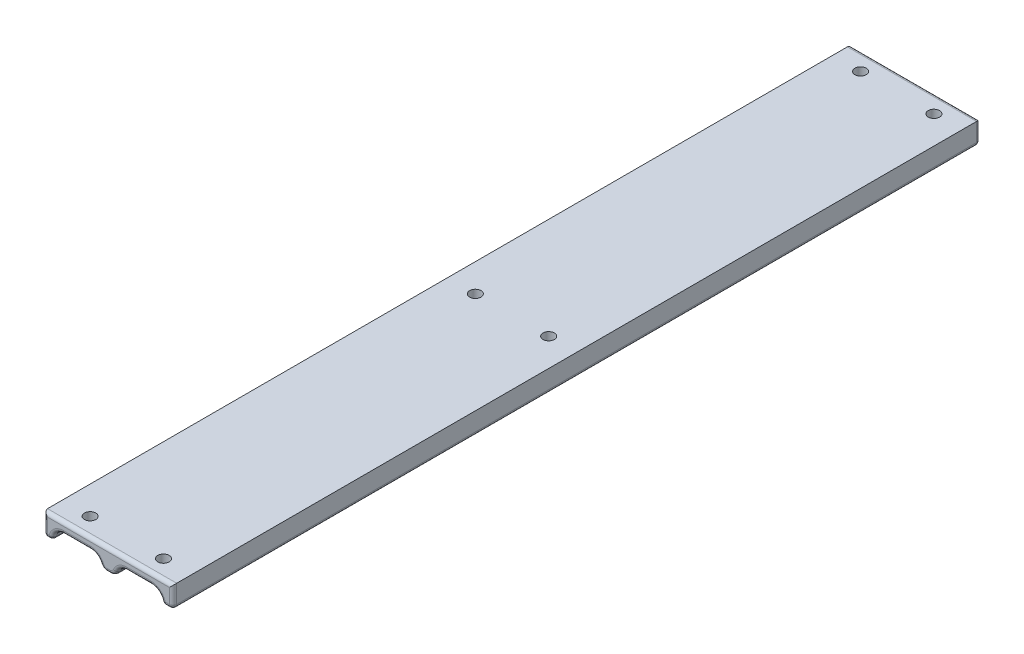
SolidWorks part; units mm, degrees
ref_plane "前视基准面" through (0, 0, 0) normal (0, 0, 1) x (1, 0, 0)
ref_plane "上视基准面" through (0, 0, 0) normal (0, 1, 0) x (1, 0, 0)
ref_plane "右视基准面" through (0, 0, 0) normal (1, 0, 0) x (0, 0, -1)
sketch "草图1" plane through (0, 0, 0) normal (0, 1, 0) x (1, 0, 0)
  line L0 (-17.6041, -110) -> (17.6041, -110)
  line L1 (17.6041, -110) -> (17.6041, 110)
  line L2 (17.6041, 110) -> (-17.6041, 110)
  line L3 (-17.6041, 110) -> (-17.6041, -110)
  circle A0 centre (10, -105) radius 1.55
  circle A1 centre (-10, -105) radius 1.55
  circle A2 centre (10, 0) radius 1.55
  circle A3 centre (-10, 0) radius 1.55
  circle A4 centre (10, 105) radius 1.55
  circle A5 centre (-10, 105) radius 1.55
extrude "凸台-拉伸1" add sketch "草图1" along normal blind 3
sketch "草图2" plane through (0, 0, 0) normal (0, -1, 0) x (1, 0, 0)
  line L1 (-17.6041, 110) -> (-15.2584, 110)
  line L2 (-17.6041, 110) -> (-17.6041, -110)
  line L3 (-17.6041, -110) -> (-15.2584, -110)
  line L4 (-17.6041, 110) -> (-17.6041, -110)
  line L5 (-17.6041, -110) -> (17.6041, -110)
  line L6 (17.6041, -110) -> (17.6041, 110)
  line L7 (17.6041, 110) -> (-17.6041, 110)
  line L8 (-17.6041, 110) -> (-17.6041, -110)
  line L9 (-17.6041, -110) -> (17.6041, -110)
  line L10 (17.6041, -110) -> (17.6041, 110)
  line L11 (17.6041, 110) -> (-17.6041, 110)
  line L12 (-15.2584, 110) -> (-15.2584, -110)
  line L13 (-2, -110) -> (-2, 110)
  line L14 (2, -110) -> (2, 110)
  line L15 (-2, 110) -> (2, 110)
  line L16 (0, -110) -> (0, 110) construction
  line L18 (14.6041, 110) -> (17.6041, 110)
  line L19 (14.6041, 110) -> (14.6041, -110)
  line L20 (14.6041, -110) -> (17.6041, -110)
  line L21 (17.6041, 110) -> (17.6041, -110)
  point P8 (0, -110)
  line M10 (-17.6041, 110) -> (-17.6041, -110)
  line M11 (-17.6041, -110) -> (17.6041, -110)
  line M12 (17.6041, -110) -> (17.6041, 110)
  line M13 (17.6041, 110) -> (-17.6041, 110)
  dimension "D2" = 2
  dimension "D3" = 2
  dimension "D4" = 3
  dimension "D1" = 0
extrude "凸台-拉伸2" add sketch "草图2" along normal blind 3 contours L19 L9 M13 M12 | L9 L16 L15 L13 | L16 L14 L11 M11 | L12 M13 M10 M11 region at (-16.4312, 0, 0) region at (-1, 0, 0) region at (1, 0, 0) region at (16.1041, 0, 0)
fillet "圆角1" radius 3 4 edges at (14.6041, 0, 0) (2, 0, 0) (-2, 0, 0) (-15.2584, 0, 0)
fillet "圆角2" radius 2 2 edges at (-2, -3, 0) (2, -3, 0)
fillet "圆角3" radius 1 32 edges at (-8.6292, 0, 110) (-14.3797, -0.8787, 110) (-16.4312, -3, 110) (-17.6041, 0, 110) (0, 3, 110) (17.6041, 0, 110) (16.1041, -3, 110) (13.7254, -0.8787, 110) (8.302, 0, 110) (3.3568, -0.49, 110) (1.5129, -2.6733, 110) (0, -3, 110) (-1.5129, -2.6733, 110) (-3.3568, -0.49, 110) (1.5129, -2.6733, -110) (3.3568, -0.49, -110) (8.302, 0, -110) (13.7254, -0.8787, -110) (16.1041, -3, -110) (17.6041, 0, -110) (0, 3, -110) (-17.6041, 0, -110) (-16.4312, -3, -110) (-14.3797, -0.8787, -110) (-8.6292, 0, -110) (-3.3568, -0.49, -110) (-1.5129, -2.6733, -110) (0, -3, -110) (-17.6041, -3, 0) (-15.2584, -3, 0) (17.6041, -3, 0) (14.6041, -3, 0)
